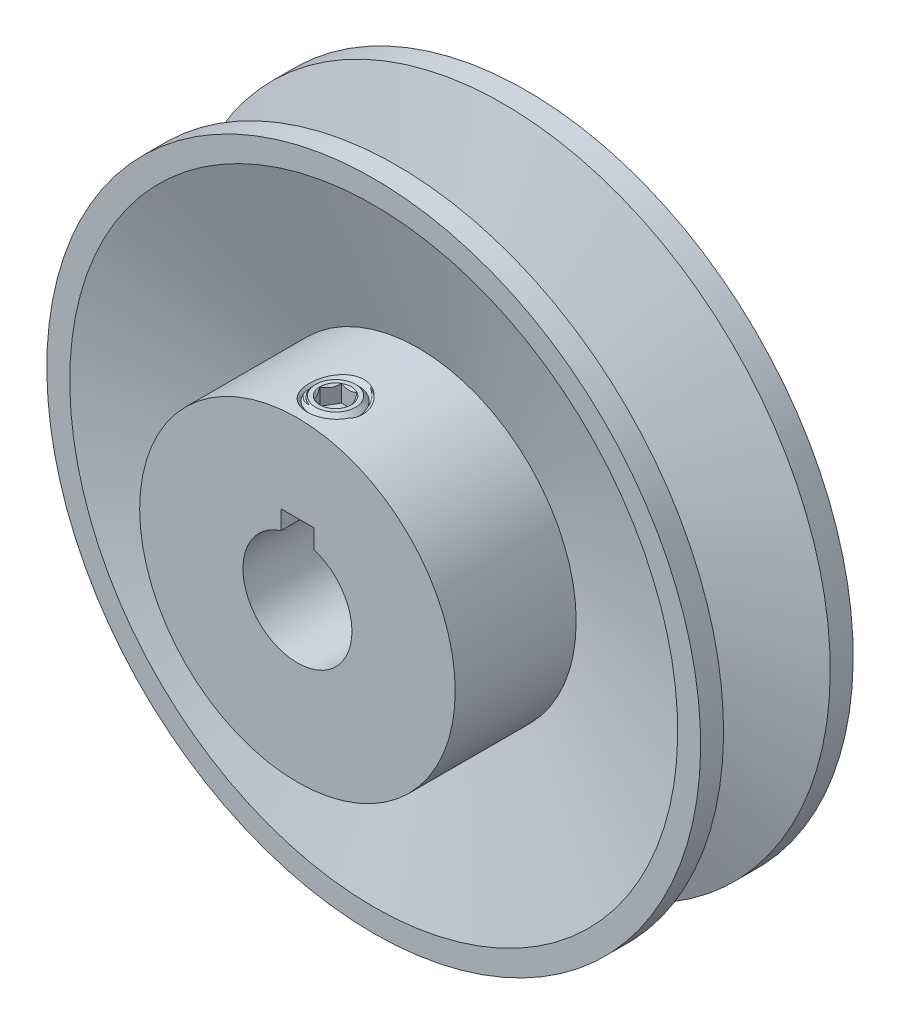
SolidWorks part; units mm, degrees
ref_plane "Front Plane" through (0, 0, 0) normal (0, 0, 1) x (1, 0, 0)
ref_plane "Top Plane" through (0, 0, 0) normal (0, 1, 0) x (1, 0, 0)
ref_plane "Right Plane" through (0, 0, 0) normal (1, 0, 0) x (0, 0, -1)
sketch "Sketch1" plane through (0, 0, 0) normal (1, 0, 0) x (0, 0, -1)
  line L0 (-22.225, 0) -> (11.1125, 0) construction
  line L1 (-7.7724, 47.625) -> (7.7724, 47.625) construction
  line L2 (7.7724, 47.625) -> (11.1125, 47.625)
  line L5 (-11.1125, 47.625) -> (11.1125, 47.625) construction
  line L7 (-11.1125, 0) -> (-11.1125, 22.987)
  line L9 (-11.1125, 44.2849) -> (-4.6011, 22.987)
  line L13 (-7.7724, 47.625) -> (-2.9189, 31.75)
  line L14 (-2.9189, 31.75) -> (2.9189, 31.75)
  line L15 (2.9189, 31.75) -> (7.7724, 47.625)
  line L16 (11.1125, 7.9375) -> (-22.225, 7.9375) construction
  line L17 (0, 47.625) -> (0, 0) construction
  line L18 (-7.7724, 47.625) -> (-11.1125, 47.625)
  line L20 (-22.225, 0) -> (-22.225, 7.9375) construction
  line L22 (4.8603, 38.1) -> (-4.8603, 38.1) construction
  line L23 (11.1125, 47.625) -> (11.1125, 0) construction
  line L24 (-4.6011, 22.987) -> (-11.1125, 22.987)
  line L26 (-11.1125, 0) -> (7.9375, 0)
  line L27 (7.9375, 20.6058) -> (3.8731, 20.6058)
  line L28 (3.8731, 20.6058) -> (11.1125, 44.2849)
  line L29 (-11.1125, 44.2849) -> (-11.1125, 47.625)
  line L31 (11.1125, 44.2849) -> (11.1125, 47.625)
  line L32 (7.9375, 0) -> (7.9375, 20.6058)
  line L33 (11.1125, 47.625) -> (11.1125, 0) construction
  line L34 (-22.225, 22.987) -> (-22.225, -22.987) construction
  line L35 (6.4134, 43.18) -> (-6.4134, 43.18) construction
  point P16 (0, 31.75)
  point P38 (-11.1125, 0)
revolve "Revolve1" add sketch "Sketch1" angle 360 about L0
sketch "Sketch2" plane through (0, 0, 0) normal (1, 0, 0) x (0, 0, -1)
  line L0 (11.1125, 0) -> (-22.225, 0) construction
  line L3 (-11.1125, 0) -> (-11.1125, 22.987)
  line L4 (-11.1125, 22.987) -> (-22.225, 22.987)
  line L5 (-22.225, 22.987) -> (-22.225, 0)
  line L8 (-22.225, 0) -> (-11.1125, 0)
revolve "Revolve2" add sketch "Sketch2" angle 360 about L0
sketch "Sketch3" plane through (0, 0, 22.225) normal (0, 0, -1) x (-1, 0, 0)
  line L0 (-2.3813, 7.9375) -> (2.3813, 7.9375) construction
  line L1 (-2.3812, 10.3188) -> (2.3813, 10.3188) construction
  line L2 (-2.3812, 10.3188) -> (-2.3813, 5.5563) construction
  line L3 (-2.3813, 5.5563) -> (2.3813, 5.5563) construction
  line L4 (2.3813, 10.3188) -> (2.3813, 5.5563) construction
  circle A0 centre (0, 0) radius 7.9375
  circle A1 centre (0, 0) radius 38.1 construction
  circle A2 centre (0, 0) radius 43.18 construction
  dimension "Keyway Wd." = 4.7625
  dimension "Keyway Dp." = 2.3813
extrude "Cut-Extrude1" cut sketch "Sketch3" along normal up to vertex (33.3375 mm away) up to point (0, 0, -11.1125)
sketch "Sketch4" plane through (0, 0, 22.225) normal (0, 0, -1) x (-1, 0, 0)
  line L0 (-2.3812, 10.3188) -> (-2.3813, 5.5563) construction
  line L1 (-2.3812, 10.3188) -> (2.3813, 10.3188) construction
  line L2 (2.3813, 10.3188) -> (2.3813, 5.5563) construction
  line L3 (-2.3813, 5.5563) -> (2.3813, 5.5563) construction
  line L4 (-2.3812, 10.3188) -> (-2.3813, 5.5563)
  line L5 (-2.3812, 10.3188) -> (2.3813, 10.3188)
  line L6 (2.3813, 10.3188) -> (2.3813, 5.5563)
  line L7 (-2.3813, 5.5563) -> (2.3813, 5.5563)
  line L8 (-2.3813, 7.9375) -> (2.3813, 7.9375) construction
  line L9 (-2.3813, 7.9375) -> (2.3813, 7.9375) construction
extrude "Cut-Extrude2" cut sketch "Sketch4" along normal up to vertex (33.3375 mm away) up to point (0, 0, -11.1125)
ref_plane "Plane1" through (0, 22.987, 0) normal (0, 1, 0) x (-1, 0, 0)
sketch "Sketch5" plane through (0, 22.987, 0) normal (0, 1, 0) x (-1, 0, 0)
  line L0 (0, 11.1125) -> (0, 22.225) construction
  line L7 (0, 20.6375) -> (0, 19.2264) construction
  circle A0 centre (0, 16.6687) radius 3.9688 construction
  circle A1 centre (0, 16.6687) radius 3.0868
  dimension "D3" = 0.8819
extrude "Cut-Extrude3" cut sketch "Sketch5" against normal up to surface (22.987 mm away) up to plane "Top Plane"
sketch "Sketch6" plane through (0, 22.987, 0) normal (0, 1, 0) x (-1, 0, 0)
  circle A0 centre (0, 16.6687) radius 3.9688 construction
  circle A1 centre (0, 16.6687) radius 3.9688
  point P3 (0, 20.6375)
curve "Helix/Spiral1" pitch 1.4111 height 24.3981 turns 17.29
sketch "Sketch7" plane through (0, 0, 0) normal (1, 0, 0) x (0, 0, -1)
  line L0 (-19.5682, 24.3981) -> (-19.5682, 22.987) construction
  line L1 (-19.5682, 22.987) -> (-20.7903, 23.6926) construction
  line L2 (-20.7903, 23.6926) -> (-19.5682, 24.3981) construction
  line L3 (-19.5682, 22.987) -> (-20.6375, 22.987) construction
  line L4 (-20.6375, 22.987) -> (-20.6375, 23.6044) construction
  line L5 (-20.6375, 23.6044) -> (-20.6375, 23.7807) construction
  line L6 (-19.721, 23.0752) -> (-19.721, 24.3099) construction
  line L7 (-20.7903, 23.6926) -> (-20.6375, 23.6926) construction
  line L8 (-19.721, 23.6926) -> (-19.5682, 23.6926) construction
  line L9 (-19.6446, 24.354) -> (-19.6446, 23.0311)
  line L10 (-19.6446, 23.0311) -> (-20.6375, 23.6044)
  line L11 (-20.6375, 23.6044) -> (-20.6375, 23.7807)
  line L12 (-20.6375, 23.7807) -> (-19.6446, 24.354)
  point P16 (-19.6446, 23.6926)
  dimension "D1" = 1.4111
  dimension "D2" = 0.1764
sweep "Cut-Sweep1" cut profiles "Sketch7" path "Helix/Spiral1"
sketch "Sketch8" plane through (0, 22.987, 0) normal (0, 1, 0) x (-1, 0, 0)
  circle A0 centre (0, 16.6687) radius 4.1215
extrude "Cut-Extrude4" cut sketch "Sketch8" against normal through all draft 45
sketch "Sketch9" plane through (0, 0, 0) normal (1, 0, 0) x (0, 0, -1)
  line L0 (-16.6687, 22.987) -> (-16.6687, 15.0495) construction
  line L1 (-20.6375, 16.1188) -> (-20.6375, 21.9177)
  line L2 (-16.6687, 22.987) -> (-20.6375, 22.987) construction
  line L3 (-16.6687, 22.987) -> (-16.6687, 15.0495)
  line L4 (-16.6687, 15.0495) -> (-20.6375, 15.0495) construction
  line L5 (-20.6375, 22.987) -> (-20.6375, 15.0495) construction
  line L6 (-19.5682, 22.987) -> (-20.6375, 21.9177)
  line L7 (-20.6375, 16.1188) -> (-19.5682, 15.0495)
  line L8 (-19.5682, 22.987) -> (-16.6687, 22.987)
  line L9 (-19.5682, 15.0495) -> (-16.6687, 15.0495)
  line L10 (-11.1125, 22.987) -> (-22.225, 22.987) construction
  line L11 (-19.5682, 22.987) -> (-20.6375, 22.987) construction
  line L12 (-20.6375, 22.987) -> (-20.6375, 21.9177) construction
revolve "Revolve3" add sketch "Sketch9" angle 360 about L0
sketch "Sketch10" plane through (0, 22.987, 0) normal (0, 1, 0) x (-1, 0, 0)
  circle A1 centre (0, 16.6687) radius 3.9688
  circle A2 centre (0, 16.6687) radius 3.9688
  dimension "D1" = 0
curve "Helix/Spiral2" pitch 1.4111 height 9.3486 turns 6.625
sketch "Sketch11" plane through (0, 0, 0) normal (1, 0, 0) x (0, 0, -1)
  line L0 (-20.7903, 23.6926) -> (-20.7903, 22.2814) construction
  line L1 (-20.7903, 22.2814) -> (-19.5682, 22.987) construction
  line L2 (-19.5682, 22.987) -> (-20.7903, 23.6926) construction
  line L4 (-19.721, 23.0752) -> (-19.721, 22.8988)
  line L5 (-19.721, 22.8988) -> (-20.6375, 22.3696)
  line L6 (-20.6375, 22.3696) -> (-20.6375, 23.6044)
  line L7 (-20.6375, 23.6044) -> (-19.721, 23.0752)
sweep "Cut-Sweep2" cut profiles "Sketch11" path "Helix/Spiral2"
sketch "Sketch12" plane through (0, 22.987, 0) normal (0, 1, 0) x (1, 0, 0)
  line L1 (2.2914, -16.6687) -> (1.1457, -14.6844)
  line L2 (1.1457, -14.6844) -> (-1.1457, -14.6844)
  line L3 (-1.1457, -14.6844) -> (-2.2914, -16.6688)
  line L4 (-2.2914, -16.6688) -> (-1.1457, -18.6531)
  line L5 (-1.1457, -18.6531) -> (1.1457, -18.6531)
  line L6 (1.1457, -18.6531) -> (2.2914, -16.6687)
  circle A0 centre (0, -16.6687) radius 1.9844 construction
extrude "Cut-Extrude5" cut sketch "Sketch12" against normal blind 2.4805
sketch "Sketch13" plane through (0, 22.987, 0) normal (0, 1, 0) x (1, 0, 0)
  circle A0 centre (0, -16.6687) radius 2.2914
extrude "Cut-Extrude6" cut sketch "Sketch13" against normal through all draft 45
equation "\"D3@Sketch5\" = \"Set Screw Pitch@Sketch5\" * 5 / 8"
equation "\"D4@Helix/Spiral1\" = \"Set Screw Pitch@Sketch5\""
equation "\"D3@Helix/Spiral1\" = \"D4@Helix/Spiral1\" + ( \"Hub Dia.@Sketch1\" / 2 ) "
equation "\"D1@Sketch7\" = \"D4@Helix/Spiral1\""
equation "\"D2@Sketch7\" = \"D1@Sketch7\" / 8"
equation "\"Set Screw Hex@Sketch12\" = \"Set Screw Dia.@Sketch5\" / 2"
equation "\"D1@Cut-Extrude5\" = \"Set Screw Hex@Sketch12\" * 5 / 8"
equation "\"D4@Helix/Spiral2\" = \"D4@Helix/Spiral1\""
equation "\"D3@Helix/Spiral2\" = \"D4@Helix/Spiral1\" + \"Set Screw Lg.@Sketch9\""
